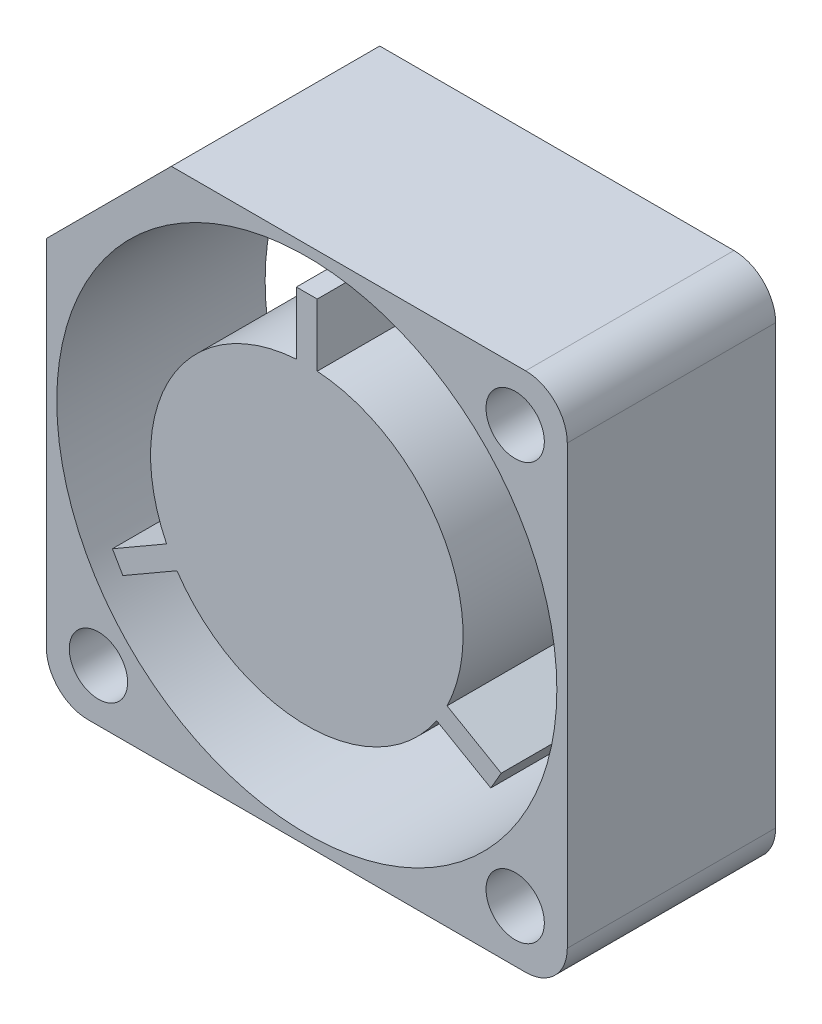
SolidWorks part; units mm, degrees
material "POM Acetal Copolymer"
ref_plane "Front Plane" through (0, 0, 0) normal (0, 0, 1) x (1, 0, 0)
ref_plane "Top Plane" through (0, 0, 0) normal (0, 1, 0) x (1, 0, 0)
ref_plane "Right Plane" through (0, 0, 0) normal (1, 0, 0) x (0, 0, -1)
sketch "Sketch1" plane through (0, 0, 0) normal (0, 0, 1) x (1, 0, 0)
  line L0 (0, 0) -> (0, 12.5) construction
  line L1 (-12.5, 12.5) -> (12.5, 12.5)
  line L2 (-12.5, 12.5) -> (-12.5, -12.5)
  line L3 (-12.5, -12.5) -> (12.5, -12.5)
  line L4 (12.5, 12.5) -> (12.5, -12.5)
  line L5 (0, 0) -> (12.5, 0) construction
  line L6 (-10, 10) -> (-10, -10) construction
  line L7 (-10, -10) -> (10, -10) construction
  line L8 (10, -10) -> (10, 10) construction
  line L9 (10, 10) -> (-10, 10) construction
  circle A1 centre (-10, 10) radius 1.4 construction
  circle A2 centre (10, 10) radius 1.4
  circle A3 centre (10, -10) radius 1.4
  circle A4 centre (-10, -10) radius 1.4
  circle A6 centre (0, 0) radius 12
  dimension "D2" = 24
  dimension "D3" = 2.8
  dimension "D1" = 25
  dimension "D4" = 20
extrude "Boss-Extrude1" add sketch "Sketch1" along normal blind 5 and the other way blind 5
fillet "Fillet1" radius 2 4 edges at (-12.5, -12.5, 0) (12.5, -12.5, 0) (12.5, 12.5, 0) (-12.5, 12.5, 0)
sketch "Sketch2" plane through (0, 0, 5) normal (0, 0, 1) x (1, 0, 0)
  line L0 (-6.7307, -3.3086) -> (-9.3288, -4.8086)
  line L1 (-0.5, 10.4833) -> (0.5, 10.4833)
  line L2 (-0.5, 10.4833) -> (-0.5, 7.4833)
  line L3 (0, 0) -> (-9.0788, -5.2417) construction
  line L4 (0.5, 10.4833) -> (0.5, 7.4833)
  line L5 (-9.3288, -4.8086) -> (-8.8288, -5.6747)
  line L6 (-8.8288, -5.6747) -> (-6.2307, -4.1747)
  line L7 (6.2307, -4.1747) -> (8.8288, -5.6747)
  line L8 (8.8288, -5.6747) -> (9.3288, -4.8086)
  line L9 (9.3288, -4.8086) -> (6.7307, -3.3086)
  line L10 (0, 0) -> (0, 10.4833) construction
  line L11 (0, 0) -> (9.0788, -5.2417) construction
  arc A0 (-0.5, 7.4833) -> (-6.7307, -3.3086) centre (0, 0) ccw
  arc A1 (-6.2307, -4.1747) -> (6.2307, -4.1747) centre (0, 0) ccw
  arc A2 (6.7307, -3.3086) -> (0.5, 7.4833) centre (0, 0) ccw
  dimension "D1" = 15
  dimension "D2" = 3
  dimension "D3" = 1
  dimension "D4" = 120
  dimension "D5" = 120
extrude "Boss-Extrude2" add sketch "Sketch2" against normal up to surface (10 mm away) separate body up to face at (12, 0, -5)
sketch "Sketch3" plane through (0, 0, 5) normal (0, 0, 1) x (1, 0, 0)
  line L0 (-6.5, 12.5) -> (-12.5, 6.5)
  line L1 (10.5, 12.5) -> (-10.5, 12.5) construction
  line L2 (-12.5, 10.5) -> (-12.5, -10.5) construction
  line L3 (-9.5, 9.5) -> (0, 0) construction
  line L4 (-12.5, 6.5) -> (-6.5, 6.5) construction
  line L5 (-6.5, 6.5) -> (-6.5, 12.5) construction
  line L6 (-12.5, 10.5) -> (-12.5, 6.5)
  line L7 (-6.5, 12.5) -> (-10.5, 12.5)
  arc A0 (-10.5, 12.5) -> (-12.5, 10.5) centre (-10.5, 10.5) ccw construction
  arc A1 (-10.5, 12.5) -> (-12.5, 10.5) centre (-10.5, 10.5) ccw
  dimension "D1" = 6
extrude "Cut-Extrude1" cut sketch "Sketch3" against normal through all
